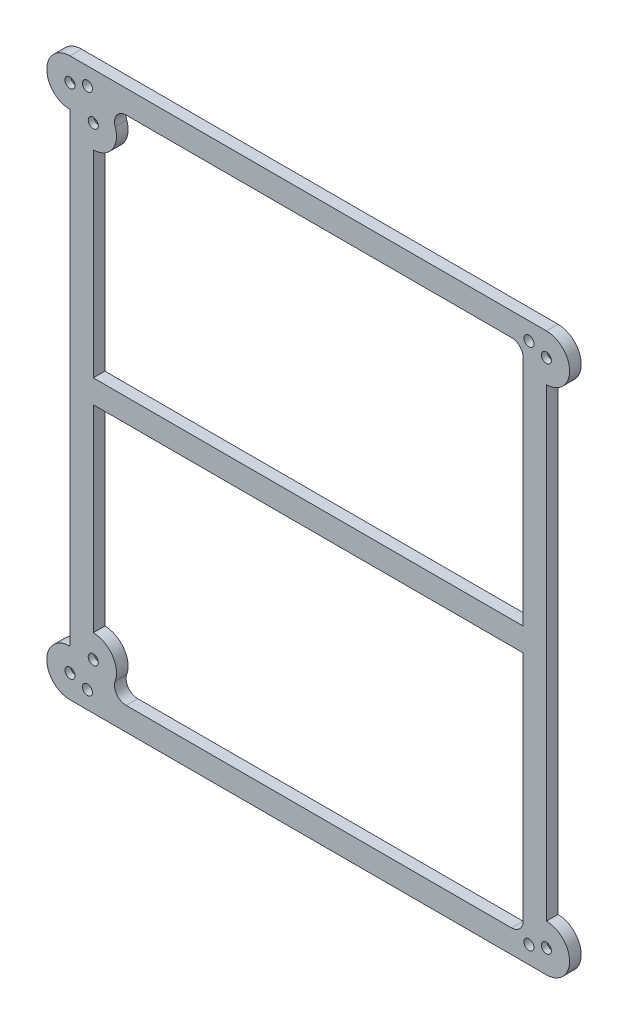
SolidWorks part; units mm, degrees
ref_plane "Front Plane" through (0, 0, 0) normal (0, 0, 1) x (1, 0, 0)
ref_plane "Top Plane" through (0, 0, 0) normal (0, 1, 0) x (1, 0, 0)
ref_plane "Right Plane" through (0, 0, 0) normal (1, 0, 0) x (0, 0, -1)
sketch "Sketch1" plane through (0, 0, 0) normal (0, 0, 1) x (1, 0, 0)
  line L0 (254, 6.35) -> (254, -273.05) construction
  line L1 (-19.05, -285.75) -> (241.3, -285.75)
  line L2 (-19.05, -285.75) -> (-19.05, 19.05)
  line L3 (-19.05, 19.05) -> (241.3, 19.05)
  line L4 (241.3, -285.75) -> (241.3, 19.05)
  line L5 (-19.05, -285.75) -> (241.3, 19.05) construction
  line L6 (-19.05, 19.05) -> (241.3, -285.75) construction
  line L7 (-6.35, 6.35) -> (228.6, 6.35)
  line L8 (-6.35, 6.35) -> (-6.35, -273.05)
  line L9 (-6.35, -273.05) -> (228.6, -273.05)
  line L10 (228.6, 6.35) -> (228.6, -273.05)
  line L11 (-6.35, 6.35) -> (228.6, -273.05) construction
  line L12 (-6.35, -273.05) -> (228.6, 6.35) construction
  circle A0 centre (-9.525, -276.225) radius 2.75
  circle A1 centre (231.775, -276.225) radius 2.75
  circle A2 centre (231.775, 9.525) radius 2.75
  circle A3 centre (-9.525, 9.525) radius 2.75
  circle A4 centre (231.775, 9.525) radius 2.75 construction
  arc A5 (241.3, 19.05) -> (241.3, -6.35) centre (241.3, 6.35) cw
  arc A6 (241.3, -260.35) -> (241.3, -285.75) centre (241.3, -273.05) cw
  arc A7 (-19.05, 19.05) -> (-19.05, -6.35) centre (-19.05, 6.35) ccw
  arc A8 (-19.05, -285.75) -> (-19.05, -260.35) centre (-19.05, -273.05) cw
  circle A9 centre (-19.05, -273.05) radius 2.75
  circle A10 centre (241.3, -273.05) radius 2.75
  circle A11 centre (241.3, 6.35) radius 2.75
  circle A12 centre (-19.05, 6.35) radius 2.75
  circle A13 centre (-6.35, -260.35) radius 2.75
  circle A14 centre (-6.35, -260.35) radius 12.7
  circle A15 centre (-6.35, -6.35) radius 12.7
  circle A16 centre (-6.35, -6.35) radius 2.75
  point P4 (111.125, -133.35)
  point P24 (111.125, -133.35)
  dimension "D1" = 12.7
  dimension "D2" = 12.7
  dimension "D3" = 12.7
extrude "Boss-Extrude1" add sketch "Sketch1" along normal blind 6.35 contours L1 L4 L3 L2 A3 A2 A1 A0 L7 L10 L9 L8 | A6 L4 | A5 L4 | A9 L2 A8 | A12 L2 A7 | A15 L2 A14 L8 | A16 L8 A15 | A16 L8 A15 | L8 A14 A13 | L8 A14 A13
fillet "Fillet1" radius 6.35 4 edges at (228.6, 6.35, 3.175) (228.6, -273.05, 3.175) (-6.35, -273.05, 3.175) (-6.35, 6.35, 3.175)
chamfer "Chamfer1" distance 3.175 angle 45 6 edges at (-16.3, 6.35, 0) (244.05, 6.35, 0) (244.05, -273.05, 0) (-16.3, -273.05, 0) (-3.6, -6.35, 0) (-3.6, -260.35, 0)
sketch "Sketch2" plane through (0, 0, 6.35) normal (0, 0, 1) x (1, 0, 0)
  line L0 (-6.35, -19.05) -> (-6.35, -247.65) construction
  line L1 (-6.35, -127) -> (228.6, -127)
  line L2 (-6.35, -127) -> (-6.35, -139.7)
  line L3 (-6.35, -139.7) -> (228.6, -139.7)
  line L4 (228.6, -127) -> (228.6, -139.7)
  line L5 (-6.35, -127) -> (228.6, -139.7) construction
  line L6 (-6.35, -139.7) -> (228.6, -127) construction
  line L7 (228.6, 0) -> (228.6, -266.7) construction
  line L8 (241.3, -260.35) -> (241.3, -6.35) construction
  point P4 (111.125, -133.35)
  point P11 (241.3, -133.35)
  dimension "D1" = 12.7
extrude "Boss-Extrude2" add sketch "Sketch2" against normal up to surface (6.35 mm away) contours L1 L4 L3 L2 up to face at (-0.425, -6.35, 0)
